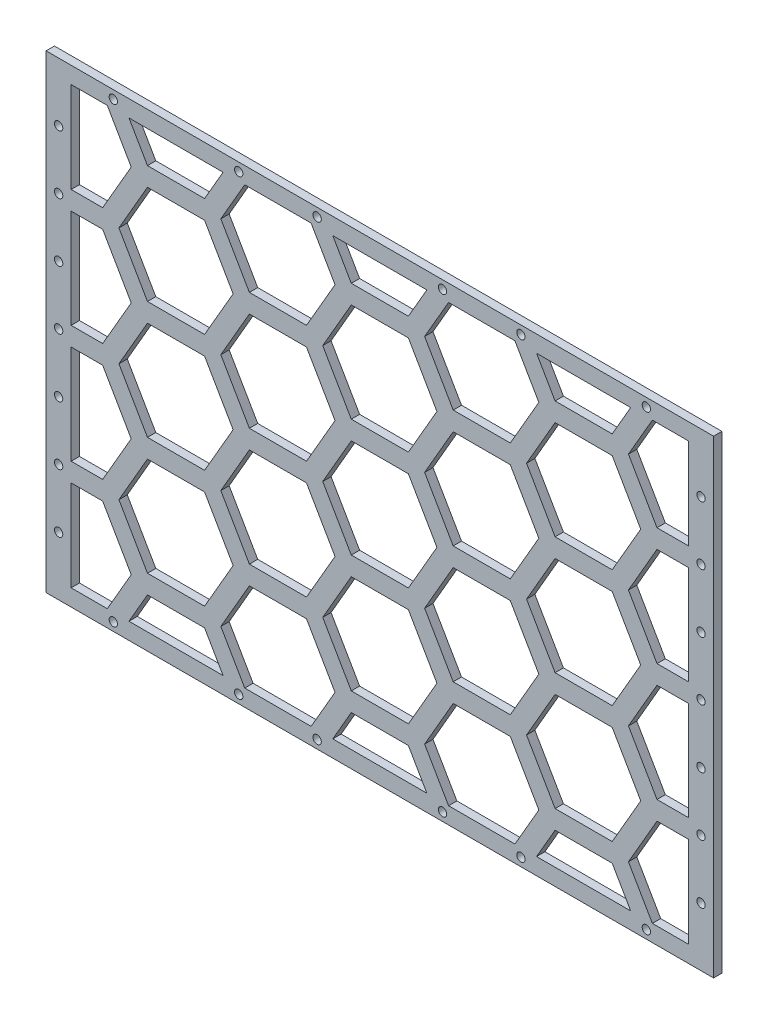
SolidWorks part; units mm, degrees
ref_plane "Front Plane" through (0, 0, 0) normal (0, 0, 1) x (1, 0, 0)
ref_plane "Top Plane" through (0, 0, 0) normal (0, 1, 0) x (1, 0, 0)
ref_plane "Right Plane" through (0, 0, 0) normal (1, 0, 0) x (0, 0, -1)
sketch "Sketch1" plane through (0, 0, 0) normal (0, 0, 1) x (1, 0, 0)
  line L1 (-40, 28.1213) -> (40, 28.1213)
  line L2 (-40, 28.1213) -> (-40, -28.1213)
  line L3 (-40, -28.1213) -> (40, -28.1213)
  line L4 (40, 28.1213) -> (40, -28.1213)
  line L7 (0, 0) -> (0, 21.6493) construction
  line L10 (-37, 26.1213) -> (37, 26.1213)
  line L11 (-37, 26.1213) -> (-37, -26.1213)
  line L12 (0, 0) -> (-30.0654, 0) construction
  line L13 (-37, -26.1213) -> (37, -26.1213)
  line L14 (37, 26.1213) -> (37, -26.1213)
  point P18 (0, 28.1213)
  point P19 (0, 26.1213)
  point P21 (37, 0)
  point P22 (40, 0)
  dimension "D2" = 74
  dimension "D3" = 80
  dimension "D5" = 52.2425
  dimension "D6" = 56.2425
extrude "Boss-Extrude1" add sketch "Sketch1" along normal blind 0.5 and the other way blind 0.5
sketch "Sketch2" plane through (0, 0, 0) normal (0, 0, 1) x (1, 0, 0)
  line L0 (0, -26.1213) -> (0, 26.1213) construction
  line L1 (-37, -1.125) -> (-37, 1.125)
  line L2 (-38, 15.2288) -> (-38, 12.9788)
  line L3 (-32.6659, 26.1213) -> (-30.0678, 26.1213)
  line L4 (-38, 0) -> (-32.5714, 0) construction
  line L5 (-32.5714, 0) -> (-28.5, 7.0519) construction
  line L6 (-28.5, 7.0519) -> (-20.3571, 7.0519) construction
  line L7 (-20.3571, 7.0519) -> (-16.2857, 0) construction
  line L8 (-16.2857, 0) -> (-8.1429, 0) construction
  line L9 (-8.1429, 0) -> (-4.0714, 7.0519) construction
  line L10 (-18.7893, 26.1213) -> (-16.1913, 26.1213)
  line L11 (-8.2373, 26.1213) -> (-5.6392, 26.1213)
  line L12 (6.9383, 26.1213) -> (4.0714, 21.1558) construction
  line L13 (-38, 14.1038) -> (-32.5714, 14.1038) construction
  line L14 (-32.5714, 14.1038) -> (-28.5, 7.0519) construction
  line L15 (-20.3571, 7.0519) -> (-16.2857, 14.1038) construction
  line L16 (-16.2857, 14.1038) -> (-20.3571, 21.1558) construction
  line L17 (-20.3571, 21.1558) -> (-28.5, 21.1558) construction
  line L18 (-32.5714, 14.1038) -> (-28.5, 21.1558) construction
  line L19 (-16.2857, 14.1038) -> (-8.1429, 14.1038) construction
  line L20 (-8.1429, 14.1038) -> (-4.0714, 7.0519) construction
  line L21 (-8.1429, 14.1038) -> (-4.0714, 21.1558) construction
  line L22 (17.4903, 26.1213) -> (20.3571, 21.1558) construction
  line L23 (31.3668, 26.1213) -> (28.5, 21.1558) construction
  line L24 (8.1429, 14.1038) -> (4.0714, 21.1558) construction
  line L25 (-31.3668, 26.1213) -> (-28.5, 21.1558) construction
  line L26 (8.1429, 14.1038) -> (4.0714, 7.0519) construction
  line L27 (16.2857, 14.1038) -> (8.1429, 14.1038) construction
  line L28 (32.5714, 14.1038) -> (28.5, 21.1558) construction
  line L29 (-17.4903, 26.1213) -> (-20.3571, 21.1558) construction
  line L30 (20.3571, 21.1558) -> (28.5, 21.1558) construction
  line L31 (-6.9383, 26.1213) -> (-4.0714, 21.1558) construction
  line L32 (-4.0714, 7.0519) -> (4.0714, 7.0519) construction
  line L33 (16.2857, 14.1038) -> (20.3571, 21.1558) construction
  line L34 (20.3571, 7.0519) -> (16.2857, 14.1038) construction
  line L35 (32.5714, 14.1038) -> (28.5, 7.0519) construction
  line L36 (-4.0714, 21.1558) -> (4.0714, 21.1558) construction
  line L37 (38, 14.1038) -> (32.5714, 14.1038) construction
  line L38 (-31.2724, 0) -> (-27.8505, 5.9269)
  line L39 (8.1429, 0) -> (4.0714, 7.0519) construction
  line L40 (16.2857, 0) -> (8.1429, 0) construction
  line L41 (20.3571, 7.0519) -> (16.2857, 0) construction
  line L42 (-27.8505, 5.9269) -> (-21.0067, 5.9269)
  line L43 (28.5, 7.0519) -> (20.3571, 7.0519) construction
  line L44 (-21.0067, 5.9269) -> (-17.5848, 0)
  line L45 (-6.8438, 0) -> (-3.4219, 5.9269)
  line L46 (32.5714, 0) -> (28.5, 7.0519) construction
  line L47 (38, 0) -> (32.5714, 0) construction
  line L48 (-37, 1.125) -> (-33.2209, 1.125)
  line L49 (-38, 12.9788) -> (-33.2209, 12.9788)
  line L50 (-33.2209, 12.9788) -> (-29.799, 7.0519)
  line L51 (-19.0581, 7.0519) -> (-15.6362, 12.9788)
  line L52 (-15.6362, 15.2288) -> (-19.0581, 21.1558)
  line L53 (-21.0067, 22.2808) -> (-27.8505, 22.2808)
  line L54 (-31.2724, 14.1038) -> (-27.8505, 20.0308)
  line L55 (-15.6362, 12.9788) -> (-8.7924, 12.9788)
  line L56 (-8.7924, 12.9788) -> (-5.3705, 7.0519)
  line L57 (-6.8438, 14.1038) -> (-3.4219, 20.0308)
  line L58 (5.6392, 26.1213) -> (3.4219, 22.2808)
  line L59 (16.1913, 26.1213) -> (19.0581, 21.1558)
  line L60 (30.0678, 26.1213) -> (27.8505, 22.2808)
  line L61 (-32.6659, 26.1213) -> (-29.799, 21.1558)
  line L62 (8.7924, 15.2288) -> (5.3705, 21.1558)
  line L63 (6.8438, 14.1038) -> (3.4219, 8.1769)
  line L64 (15.6362, 15.2288) -> (8.7924, 15.2288)
  line L65 (-18.7893, 26.1213) -> (-21.0067, 22.2808)
  line L66 (33.2209, 15.2288) -> (29.799, 21.1558)
  line L67 (-8.2373, 26.1213) -> (-5.3705, 21.1558)
  line L68 (-15.6362, -1.125) -> (-8.7924, -1.125)
  line L69 (21.0067, 20.0308) -> (27.8505, 20.0308)
  line L70 (17.5848, 14.1038) -> (21.0067, 20.0308)
  line L71 (21.0067, 8.1769) -> (17.5848, 14.1038)
  line L72 (-3.4219, 20.0308) -> (3.4219, 20.0308)
  line L73 (31.2724, 14.1038) -> (27.8505, 8.1769)
  line L74 (38, 15.2288) -> (33.2209, 15.2288)
  line L75 (8.7924, 1.125) -> (5.3705, 7.0519)
  line L76 (19.0581, 7.0519) -> (15.6362, 1.125)
  line L77 (27.8505, 8.1769) -> (21.0067, 8.1769)
  line L78 (33.2209, 1.125) -> (29.799, 7.0519)
  line L79 (-33.2209, 1.125) -> (-29.799, 7.0519)
  line L80 (-27.8505, 8.1769) -> (-21.0067, 8.1769)
  line L81 (-19.0581, 7.0519) -> (-15.6362, 1.125)
  line L82 (-8.7924, 1.125) -> (-5.3705, 7.0519)
  line L83 (-37, -1.125) -> (-33.2209, -1.125)
  line L84 (8.2373, 26.1213) -> (5.3705, 21.1558)
  line L85 (18.7893, 26.1213) -> (21.0067, 22.2808)
  line L86 (-38, 15.2288) -> (-33.2209, 15.2288)
  line L87 (-31.2724, 14.1038) -> (-27.8505, 8.1769)
  line L88 (-21.0067, 8.1769) -> (-17.5848, 14.1038)
  line L89 (-17.5848, 14.1038) -> (-21.0067, 20.0308)
  line L90 (-21.0067, 20.0308) -> (-27.8505, 20.0308)
  line L91 (-33.2209, 15.2288) -> (-29.799, 21.1558)
  line L92 (-15.6362, 15.2288) -> (-8.7924, 15.2288)
  line L93 (-6.8438, 14.1038) -> (-3.4219, 8.1769)
  line L94 (-8.7924, 15.2288) -> (-5.3705, 21.1558)
  line L95 (32.6659, 26.1213) -> (29.799, 21.1558)
  line L96 (6.8438, 14.1038) -> (3.4219, 20.0308)
  line L97 (8.7924, 12.9788) -> (5.3705, 7.0519)
  line L98 (-30.0678, 26.1213) -> (-27.8505, 22.2808)
  line L99 (15.6362, 12.9788) -> (8.7924, 12.9788)
  line L100 (31.2724, 14.1038) -> (27.8505, 20.0308)
  line L101 (21.0067, 22.2808) -> (27.8505, 22.2808)
  line L102 (-16.1913, 26.1213) -> (-19.0581, 21.1558)
  line L103 (15.6362, 15.2288) -> (19.0581, 21.1558)
  line L104 (-5.6392, 26.1213) -> (-3.4219, 22.2808)
  line L105 (-3.4219, 8.1769) -> (3.4219, 8.1769)
  line L106 (19.0581, 7.0519) -> (15.6362, 12.9788)
  line L107 (33.2209, 12.9788) -> (29.799, 7.0519)
  line L108 (38, 12.9788) -> (33.2209, 12.9788)
  line L109 (-3.4219, 22.2808) -> (3.4219, 22.2808)
  line L110 (6.8438, 0) -> (3.4219, 5.9269)
  line L111 (21.0067, 5.9269) -> (17.5848, 0)
  line L112 (27.8505, 5.9269) -> (21.0067, 5.9269)
  line L113 (31.2724, 0) -> (27.8505, 5.9269)
  line L114 (8.2373, 26.1213) -> (5.6392, 26.1213)
  line L115 (18.7893, 26.1213) -> (16.1913, 26.1213)
  line L116 (32.6659, 26.1213) -> (30.0678, 26.1213)
  line L117 (38, 15.2288) -> (38, 12.9788)
  line L118 (-3.4219, 5.9269) -> (3.4219, 5.9269)
  line L119 (8.7924, 1.125) -> (15.6362, 1.125)
  line L120 (38, -1.125) -> (38, 1.125)
  line L121 (-38, 0) -> (38, 0) construction
  line L122 (32.5714, 0) -> (28.5, -7.0519) construction
  line L123 (28.5, -7.0519) -> (20.3571, -7.0519) construction
  line L124 (20.3571, -7.0519) -> (16.2857, 0) construction
  line L125 (8.1429, 0) -> (4.0714, -7.0519) construction
  line L126 (38, -14.1038) -> (32.5714, -14.1038) construction
  line L127 (-4.0714, -21.1558) -> (4.0714, -21.1558) construction
  line L128 (32.5714, -14.1038) -> (28.5, -7.0519) construction
  line L129 (20.3571, -7.0519) -> (16.2857, -14.1038) construction
  line L130 (16.2857, -14.1038) -> (20.3571, -21.1558) construction
  line L131 (-4.0714, -7.0519) -> (4.0714, -7.0519) construction
  line L132 (-6.9383, -26.1213) -> (-4.0714, -21.1558) construction
  line L133 (20.3571, -21.1558) -> (28.5, -21.1558) construction
  line L134 (-17.4903, -26.1213) -> (-20.3571, -21.1558) construction
  line L135 (32.5714, -14.1038) -> (28.5, -21.1558) construction
  line L136 (16.2857, -14.1038) -> (8.1429, -14.1038) construction
  line L137 (8.1429, -14.1038) -> (4.0714, -7.0519) construction
  line L138 (-31.3668, -26.1213) -> (-28.5, -21.1558) construction
  line L139 (8.1429, -14.1038) -> (4.0714, -21.1558) construction
  line L140 (31.3668, -26.1213) -> (28.5, -21.1558) construction
  line L141 (17.4903, -26.1213) -> (20.3571, -21.1558) construction
  line L142 (-8.1429, -14.1038) -> (-4.0714, -21.1558) construction
  line L143 (-8.1429, -14.1038) -> (-4.0714, -7.0519) construction
  line L144 (-16.2857, -14.1038) -> (-8.1429, -14.1038) construction
  line L145 (-32.5714, -14.1038) -> (-28.5, -21.1558) construction
  line L146 (-20.3571, -21.1558) -> (-28.5, -21.1558) construction
  line L147 (-16.2857, -14.1038) -> (-20.3571, -21.1558) construction
  line L148 (-20.3571, -7.0519) -> (-16.2857, -14.1038) construction
  line L149 (-32.5714, -14.1038) -> (-28.5, -7.0519) construction
  line L150 (-38, -14.1038) -> (-32.5714, -14.1038) construction
  line L151 (6.9383, -26.1213) -> (4.0714, -21.1558) construction
  line L152 (-8.1429, 0) -> (-4.0714, -7.0519) construction
  line L153 (-20.3571, -7.0519) -> (-16.2857, 0) construction
  line L154 (-28.5, -7.0519) -> (-20.3571, -7.0519) construction
  line L155 (-32.5714, 0) -> (-28.5, -7.0519) construction
  line L156 (-15.6362, 1.125) -> (-8.7924, 1.125)
  line L157 (-3.4219, -5.9269) -> (3.4219, -5.9269)
  line L158 (38, -15.2288) -> (38, -12.9788)
  line L159 (32.6659, -26.1213) -> (30.0678, -26.1213)
  line L160 (18.7893, -26.1213) -> (16.1913, -26.1213)
  line L161 (8.2373, -26.1213) -> (5.6392, -26.1213)
  line L162 (31.2724, 0) -> (27.8505, -5.9269)
  line L163 (27.8505, -5.9269) -> (21.0067, -5.9269)
  line L164 (21.0067, -5.9269) -> (17.5848, 0)
  line L165 (6.8438, 0) -> (3.4219, -5.9269)
  line L166 (-3.4219, -22.2808) -> (3.4219, -22.2808)
  line L167 (38, -12.9788) -> (33.2209, -12.9788)
  line L168 (33.2209, -12.9788) -> (29.799, -7.0519)
  line L169 (19.0581, -7.0519) -> (15.6362, -12.9788)
  line L170 (-3.4219, -8.1769) -> (3.4219, -8.1769)
  line L171 (-5.6392, -26.1213) -> (-3.4219, -22.2808)
  line L172 (15.6362, -15.2288) -> (19.0581, -21.1558)
  line L173 (-16.1913, -26.1213) -> (-19.0581, -21.1558)
  line L174 (21.0067, -22.2808) -> (27.8505, -22.2808)
  line L175 (31.2724, -14.1038) -> (27.8505, -20.0308)
  line L176 (15.6362, -12.9788) -> (8.7924, -12.9788)
  line L177 (-30.0678, -26.1213) -> (-27.8505, -22.2808)
  line L178 (8.7924, -12.9788) -> (5.3705, -7.0519)
  line L179 (6.8438, -14.1038) -> (3.4219, -20.0308)
  line L180 (32.6659, -26.1213) -> (29.799, -21.1558)
  line L181 (-8.7924, -15.2288) -> (-5.3705, -21.1558)
  line L182 (-6.8438, -14.1038) -> (-3.4219, -8.1769)
  line L183 (-15.6362, -15.2288) -> (-8.7924, -15.2288)
  line L184 (-33.2209, -15.2288) -> (-29.799, -21.1558)
  line L185 (-21.0067, -20.0308) -> (-27.8505, -20.0308)
  line L186 (-17.5848, -14.1038) -> (-21.0067, -20.0308)
  line L187 (-21.0067, -8.1769) -> (-17.5848, -14.1038)
  line L188 (-31.2724, -14.1038) -> (-27.8505, -8.1769)
  line L189 (-38, -15.2288) -> (-33.2209, -15.2288)
  line L190 (18.7893, -26.1213) -> (21.0067, -22.2808)
  line L191 (8.2373, -26.1213) -> (5.3705, -21.1558)
  line L192 (33.2209, 1.125) -> (38, 1.125)
  line L193 (-8.7924, -1.125) -> (-5.3705, -7.0519)
  line L194 (-19.0581, -7.0519) -> (-15.6362, -1.125)
  line L195 (-27.8505, -8.1769) -> (-21.0067, -8.1769)
  line L196 (-33.2209, -1.125) -> (-29.799, -7.0519)
  line L197 (33.2209, -1.125) -> (29.799, -7.0519)
  line L198 (27.8505, -8.1769) -> (21.0067, -8.1769)
  line L199 (19.0581, -7.0519) -> (15.6362, -1.125)
  line L200 (8.7924, -1.125) -> (5.3705, -7.0519)
  line L201 (38, -15.2288) -> (33.2209, -15.2288)
  line L202 (31.2724, -14.1038) -> (27.8505, -8.1769)
  line L203 (-3.4219, -20.0308) -> (3.4219, -20.0308)
  line L204 (21.0067, -8.1769) -> (17.5848, -14.1038)
  line L205 (17.5848, -14.1038) -> (21.0067, -20.0308)
  line L206 (21.0067, -20.0308) -> (27.8505, -20.0308)
  line L208 (-8.2373, -26.1213) -> (-5.3705, -21.1558)
  line L209 (33.2209, -15.2288) -> (29.799, -21.1558)
  line L210 (-18.7893, -26.1213) -> (-21.0067, -22.2808)
  line L211 (15.6362, -15.2288) -> (8.7924, -15.2288)
  line L212 (6.8438, -14.1038) -> (3.4219, -8.1769)
  line L213 (8.7924, -15.2288) -> (5.3705, -21.1558)
  line L214 (-32.6659, -26.1213) -> (-29.799, -21.1558)
  line L215 (30.0678, -26.1213) -> (27.8505, -22.2808)
  line L216 (16.1913, -26.1213) -> (19.0581, -21.1558)
  line L217 (5.6392, -26.1213) -> (3.4219, -22.2808)
  line L218 (-6.8438, -14.1038) -> (-3.4219, -20.0308)
  line L219 (-8.7924, -12.9788) -> (-5.3705, -7.0519)
  line L220 (-15.6362, -12.9788) -> (-8.7924, -12.9788)
  line L221 (-31.2724, -14.1038) -> (-27.8505, -20.0308)
  line L222 (-21.0067, -22.2808) -> (-27.8505, -22.2808)
  line L223 (-15.6362, -15.2288) -> (-19.0581, -21.1558)
  line L224 (-19.0581, -7.0519) -> (-15.6362, -12.9788)
  line L225 (-33.2209, -12.9788) -> (-29.799, -7.0519)
  line L226 (-38, -12.9788) -> (-33.2209, -12.9788)
  line L227 (33.2209, -1.125) -> (38, -1.125)
  line L228 (-6.8438, 0) -> (-3.4219, -5.9269)
  line L229 (-21.0067, -5.9269) -> (-17.5848, 0)
  line L230 (-27.8505, -5.9269) -> (-21.0067, -5.9269)
  line L231 (-31.2724, 0) -> (-27.8505, -5.9269)
  line L232 (-8.2373, -26.1213) -> (-5.6392, -26.1213)
  line L233 (-18.7893, -26.1213) -> (-16.1913, -26.1213)
  line L234 (-32.6659, -26.1213) -> (-30.0678, -26.1213)
  line L235 (-38, -15.2288) -> (-38, -12.9788)
  line L236 (15.6362, -1.125) -> (8.7924, -1.125)
  line L237 (-37, 26.1213) -> (-37, -26.1213) construction
  circle A0 centre (0, 0) radius 7.0519 construction
  point P4 (0, 21.1558)
  point P17 (0, 7.0519)
  point P46 (0, 5.9269)
  point P49 (0, 22.2808)
  point P52 (0, 8.1769)
  point P98 (0, 20.0308)
  point P232 (0, -20.0308)
  point P233 (0, -8.1769)
  point P234 (0, -22.2808)
  point P235 (0, -5.9269)
  point P236 (0, -7.0519)
  point P237 (0, -21.1558)
  dimension "D1" = 1.125
  dimension "D4" = 1.125
  dimension "D5" = 1.125
  dimension "D2" = 1.125
  dimension "D3" = 1.125
  dimension "D6" = 2.25
  dimension "D8" = 1.125
  dimension "D9" = 1.125
extrude "Boss-Extrude2" add sketch "Sketch2" along normal blind 0.5 and the other way blind 0.5
sketch "Sketch3" plane through (0, 0, 0.5) normal (0, 0, 1) x (1, 0, 0)
  line L0 (0, 0) -> (-50.1494, 0) construction
  line L1 (0, 0) -> (0, 34.72) construction
  line L2 (-38.5, 21.0909) -> (-38.5, 14.0606) construction
  line L3 (-37, 26.1213) -> (-38.5, 21.0909) construction
  line L4 (-38.5, 21.0909) -> (-40, 26.1213) construction
  line L5 (-40, 28.1213) -> (-40, -28.1213) construction
  line L6 (-32.6659, 26.1213) -> (-37, 26.1213) construction
  line L7 (-18.7893, 26.1213) -> (-21.0067, 22.2808) construction
  line L8 (-38.5, 14.0606) -> (-38.5, 7.0303) construction
  line L9 (-38.5, 7.0303) -> (-38.5, 0) construction
  line L10 (-38.5, 21.0909) -> (-38.5, 28.1213) construction
  line L11 (40, 28.1213) -> (-40, 28.1213) construction
  line L12 (-28.8248, 21.7183) -> (-31.9442, 27.1213) construction
  line L13 (-8.2373, 26.1213) -> (-5.3705, 21.1558) construction
  line L14 (-27.8505, 22.2808) -> (-30.0678, 26.1213) construction
  line L15 (-29.799, 21.1558) -> (-27.8505, 22.2808) construction
  line L16 (-21.0067, 22.2808) -> (-19.0581, 21.1558) construction
  line L17 (-15.6362, 15.2288) -> (-19.0581, 21.1558) construction
  line L19 (-20.0324, 21.7183) -> (-16.913, 27.1213) construction
  line L21 (-5.3705, 21.1558) -> (-8.7924, 15.2288) construction
  line L22 (-5.3705, 21.1558) -> (-3.4219, 22.2808) construction
  line L24 (-4.3962, 21.7183) -> (-7.5156, 27.1213) construction
  line L25 (-32.6659, 26.1213) -> (-31.9442, 27.1213) construction
  line L26 (-31.9442, 27.1213) -> (-32.6659, 28.1213) construction
  line L27 (-32.6659, 28.1213) -> (-32.6659, 26.1213) construction
  line L28 (-31.9442, 27.1213) -> (-16.913, 27.1213) construction
  line L29 (-16.913, 27.1213) -> (-7.5156, 27.1213) construction
  circle A0 centre (-38.5, 21.0909) radius 0.5
  circle A1 centre (-38.5, 14.0606) radius 0.5
  circle A2 centre (-38.5, 7.0303) radius 0.5
  circle A3 centre (-38.5, 0) radius 0.5
  circle A4 centre (-31.9442, 27.1213) radius 0.5
  circle A5 centre (-7.5156, -27.1213) radius 0.5
  circle A6 centre (-16.913, 27.1213) radius 0.5
  circle A7 centre (-7.5156, 27.1213) radius 0.5
  circle A8 centre (-16.913, -27.1213) radius 0.5
  circle A9 centre (-31.9442, -27.1213) radius 0.5
  circle A10 centre (-38.5, -7.0303) radius 0.5
  circle A11 centre (-38.5, -14.0606) radius 0.5
  circle A12 centre (-38.5, -21.0909) radius 0.5
  circle A13 centre (7.5156, 27.1213) radius 0.5
  circle A14 centre (16.913, 27.1213) radius 0.5
  circle A15 centre (31.9442, 27.1213) radius 0.5
  circle A16 centre (38.5, 21.0909) radius 0.5
  circle A17 centre (38.5, 7.0303) radius 0.5
  circle A18 centre (38.5, 14.0606) radius 0.5
  circle A19 centre (38.5, -21.0909) radius 0.5
  circle A20 centre (38.5, -14.0606) radius 0.5
  circle A21 centre (38.5, -7.0303) radius 0.5
  circle A22 centre (31.9442, -27.1213) radius 0.5
  circle A23 centre (16.913, -27.1213) radius 0.5
  circle A24 centre (7.5156, -27.1213) radius 0.5
  circle A25 centre (38.5, 0) radius 0.5
  point P37 (-28.8248, 21.7183)
  point P38 (-20.0324, 21.7183)
  point P59 (-4.3962, 21.7183)
  dimension "D1" = 1
extrude "Cut-Extrude2" cut sketch "Sketch3" against normal blind 1
